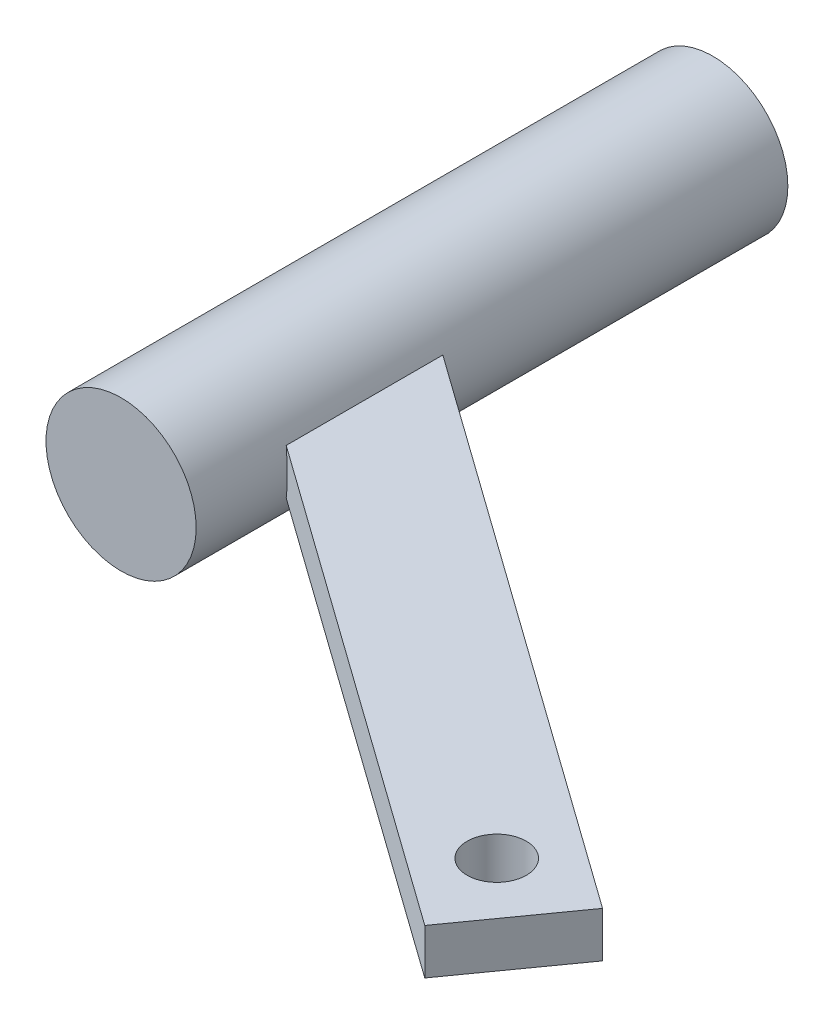
SolidWorks part; units mm, degrees
ref_plane "Alzado" through (0, 0, 0) normal (0, 0, 1) x (1, 0, 0)
ref_plane "Planta" through (0, 0, 0) normal (0, 1, 0) x (1, 0, 0)
ref_plane "Vista lateral" through (0, 0, 0) normal (1, 0, 0) x (0, 0, -1)
sketch "Sketch1" plane through (0, 0, 0) normal (0, 0, 1) x (1, 0, 0)
  circle A0 centre (0, 0) radius 16.5
  dimension "D1" = 33
extrude "Boss-Extrude1" add sketch "Sketch1" along normal blind 130
sketch "Sketch2" plane through (0, 0, 0) normal (0, 1, 0) x (1, 0, 0)
  line L0 (0, -98.2143) -> (122.2854, -185.561)
  line L1 (0, -18.15) -> (0, 18.15) construction
  line L2 (122.2854, -185.561) -> (138.56, -162.7764)
  line L3 (138.56, -162.7764) -> (0, -63.805)
  line L4 (0, -63.805) -> (0, -98.2143)
  line L5 (16.5, -130) -> (16.5, 0) construction
  line L6 (-16.5, -130) -> (16.5, -130) construction
  line L7 (16.5, -130) -> (16.5, 0) construction
  point P4 (16.5, -110)
  point P11 (16.5, -75.5907)
  dimension "D1" = 28
  dimension "D2" = 20
  dimension "D3" = 130
  dimension "D4" = 150
extrude "Boss-Extrude2" add sketch "Sketch2" along normal blind 5 and the other way blind 5
sketch "Sketch3" plane through (0, 5, 0) normal (0, 1, 0) x (1, 0, 0)
  line L0 (15.7242, -109.4458) -> (122.2854, -185.561) construction
  line L1 (122.2854, -185.561) -> (138.56, -162.7764) construction
  circle A0 centre (117.403, -164.8689) radius 6.5
  dimension "D1" = 13
  dimension "D2" = 14
  dimension "D3" = 16
extrude "Cut-Extrude1" cut sketch "Sketch3" against normal blind 20
